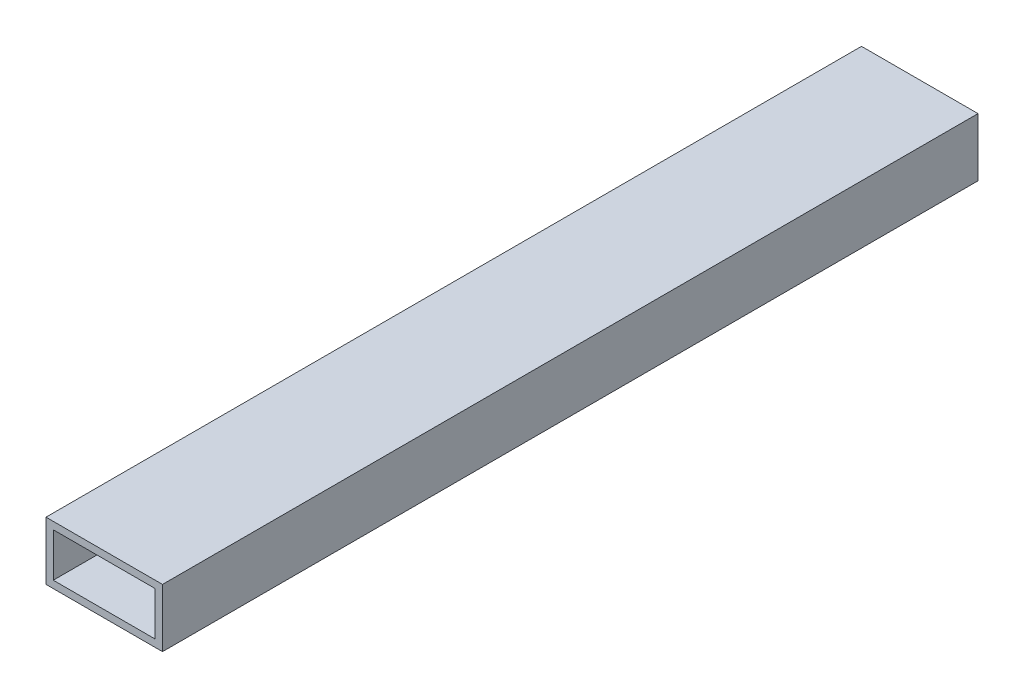
SolidWorks part; units mm, degrees
material "6061-T6 (SS)"
ref_plane "Front Plane" through (0, 0, 0) normal (0, 0, 1) x (1, 0, 0)
ref_plane "Top Plane" through (0, 0, 0) normal (0, 1, 0) x (1, 0, 0)
ref_plane "Right Plane" through (0, 0, 0) normal (1, 0, 0) x (0, 0, -1)
sketch "Sketch1" plane through (0, 0, 0) normal (0, 0, 1) x (1, 0, 0)
  line L0 (-22.225, 9.525) -> (22.225, 9.525)
  line L1 (-25.4, 12.7) -> (25.4, 12.7)
  line L2 (-25.4, 12.7) -> (-25.4, -12.7)
  line L3 (-25.4, -12.7) -> (25.4, -12.7)
  line L4 (25.4, 12.7) -> (25.4, -12.7)
  line L5 (22.225, 9.525) -> (22.225, -9.525)
  line L6 (-22.225, -9.525) -> (22.225, -9.525)
  line L7 (-22.225, 9.525) -> (-22.225, -9.525)
  line L8 (-25.4, 12.7) -> (25.4, -12.7) construction
  line L9 (25.4, 12.7) -> (-25.4, -12.7) construction
  point P5 (0, 0)
  dimension "D1" = 50.8
  dimension "D2" = 25.4
  dimension "D3" = 3.175
extrude "Boss-Extrude1" add sketch "Sketch1" along normal mid plane 355.6
